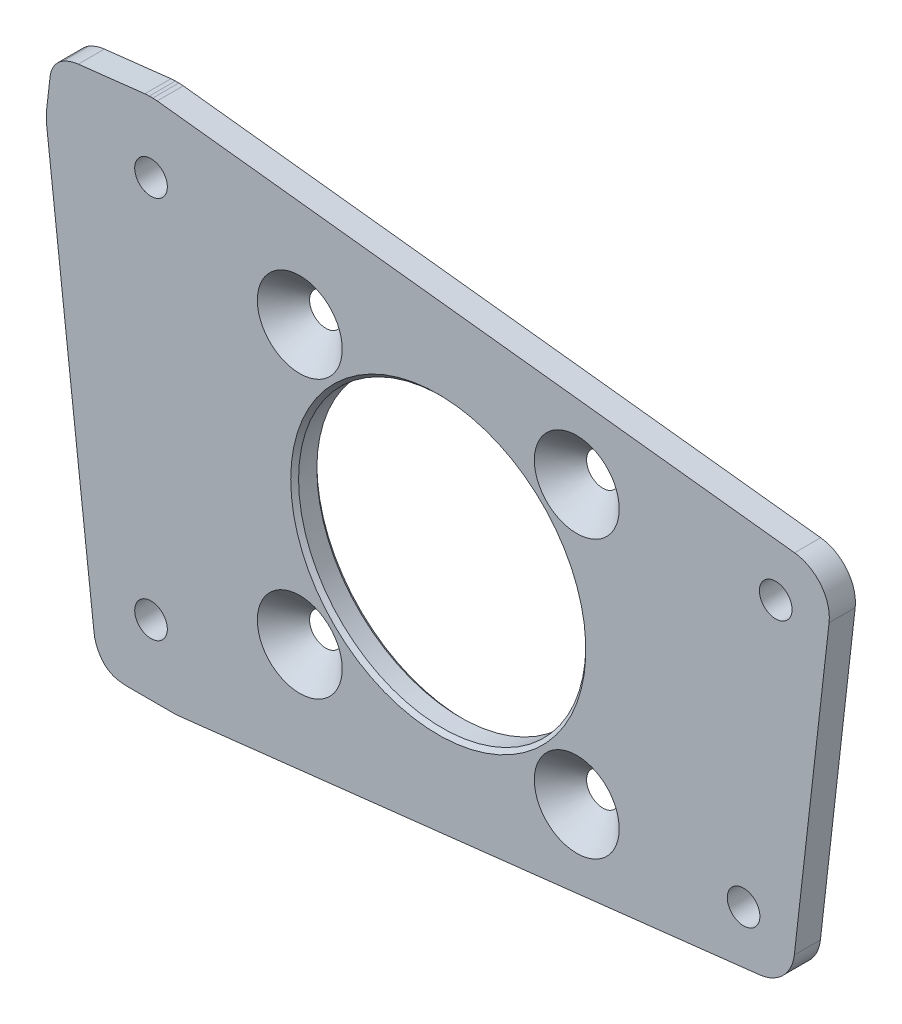
SolidWorks part; units mm, degrees
ref_plane "Płaszczyzna przednia" through (0, 0, 0) normal (0, 0, 1) x (1, 0, 0)
ref_plane "Płaszczyzna górna" through (0, 0, 0) normal (0, 1, 0) x (1, 0, 0)
ref_plane "Płaszczyzna prawa" through (0, 0, 0) normal (1, 0, 0) x (0, 0, -1)
sketch "Szkic1" plane through (0, 0, 0) normal (0, 0, 1) x (1, 0, 0)
  line L0 (0, 0) -> (-23.297, 23.297) construction
  line L1 (-27, -20) -> (27, -20)
  line L2 (-30, -17) -> (-30, 17)
  line L3 (-27, 20) -> (27, 20)
  line L4 (30, -17) -> (30, 17)
  line L5 (-30, -20) -> (30, 20) construction
  line L6 (-30, 20) -> (30, -20) construction
  line L7 (0, 0) -> (25.2349, 25.2349) construction
  arc A0 (27, 20) -> (30, 17) centre (27, 17) cw
  arc A1 (27, -20) -> (30, -17) centre (27, -17) ccw
  arc A2 (-27, -20) -> (-30, -17) centre (-27, -17) cw
  arc A3 (-30, 17) -> (-27, 20) centre (-27, 17) cw
  circle A4 centre (0, 0) radius 11
  circle A5 centre (-22, 14.6667) radius 1.25
  circle A8 centre (-10.6066, -10.6066) radius 1.25
  circle A9 centre (10.6066, -10.6066) radius 1.25
  circle A10 centre (10.6066, 10.6066) radius 1.25
  circle A11 centre (-10.6066, 10.6066) radius 1.25
  circle A12 centre (0, 0) radius 15 construction
  point P0 (0, 0)
  dimension "D3" = 3
  dimension "D4" = 30
  dimension "D6" = 2.5
  dimension "D7" = 2.5
  dimension "D8" = 2.5
  dimension "D9" = 2.5
  dimension "D10" = 22
  dimension "D11" = 2.5
  dimension "D1" = 60
  dimension "D2" = 40
  dimension "D5" = 45
  dimension "D12" = 8
extrude "Dodanie-wyciągnięcie1" add sketch "Szkic1" along normal blind 2
chamfer "Sfazowanie1" distance 0.3 angle 45 2 edges at (11, 0, 0) (11, 0, 2)
chamfer "Sfazowanie2" distance 2 angle 45 4 edges at (-9.3566, -10.6066, 2) (11.8566, -10.6066, 2) (11.8566, 10.6066, 2) (-9.3566, 10.6066, 2)
sketch "Szkic2" plane through (0, 0, 2) normal (0, 0, 1) x (1, 0, 0)
  line L9 (26.0813, 25.5127) -> (-27.5716, 19.3997)
  line L10 (-30.2127, 16.0794) -> (-26.3638, -17.7021)
  line L11 (-23.0435, -20.3432) -> (30.6094, -14.2302)
  line L12 (33.2505, -10.9099) -> (29.4016, 22.8716)
  arc A8 (29.4016, 22.8716) -> (26.0813, 25.5127) centre (26.4209, 22.532) ccw
  arc A9 (-27.5716, 19.3997) -> (-30.2127, 16.0794) centre (-27.232, 16.419) ccw
  arc A10 (-26.3638, -17.7021) -> (-23.0435, -20.3432) centre (-23.3831, -17.3625) ccw
  arc A11 (30.6094, -14.2302) -> (33.2505, -10.9099) centre (30.2698, -11.2495) ccw
sketch "Szkic3" plane through (0, 0, 0) normal (0, 0, 1) x (1, 0, 0)
  line L0 (-22, 14.6667) -> (-22, -14.6667) construction
  line L1 (25.8424, 10.5577) -> (-22, 14.6667) construction
  line L2 (-22, 14.6667) -> (23.383, -11.0277) construction
  line L3 (26, 16) -> (-22, 14.6667) construction
  line L4 (-22, 14.6667) -> (25.0697, 5.1682) construction
  line L5 (26, -5.725) -> (-22, 14.6667) construction
  line L6 (-22, 14.6667) -> (20.1826, -16) construction
  line L7 (-18.6794, -14.4781) -> (-22, 14.6667) construction
  line L8 (-22, 14.6667) -> (-25.3206, -14.4781) construction
  line L9 (-30, 17) -> (-30, -17) construction
  line L10 (-27, -20) -> (27, -20) construction
  line L11 (-27, -20) -> (27, -20) construction
  line L12 (30, -17) -> (30, 17) construction
  line L14 (27, 20) -> (-27, 20) construction
  line L15 (30, -17) -> (30, 17) construction
  circle A3 centre (-22, 14.6667) radius 29.3333 construction
  circle A4 centre (-22, 14.6667) radius 52.1519 construction
  arc A9 (-18.5379, -15.7201) -> (-18.8209, -13.2361) centre (-18.6794, -14.4781) ccw construction
  arc A10 (-25.4621, -15.7201) -> (-18.5379, -15.7201) centre (-22, 14.6667) ccw construction
  arc A11 (-25.1791, -13.2361) -> (-25.4621, -15.7201) centre (-25.3206, -14.4781) ccw construction
  arc A12 (-25.1791, -13.2361) -> (-18.8209, -13.2361) centre (-22, 14.6667) ccw construction
  circle A13 centre (-22, 14.6667) radius 48.0185 construction
  arc A18 (27.1505, -6.2137) -> (24.8495, -5.2362) centre (26, -5.725) ccw construction
  arc A19 (21.1937, -16.735) -> (27.1505, -6.2137) centre (-22, 14.6667) ccw construction
  arc A20 (19.1716, -15.265) -> (21.1937, -16.735) centre (20.1826, -16) ccw construction
  arc A21 (19.1716, -15.265) -> (24.8495, -5.2362) centre (-22, 14.6667) ccw construction
  circle A22 centre (-22, -14.6667) radius 1.25
  arc A27 (23.8444, 5.4154) -> (24.7505, 15.9653) centre (-22, 14.6667) ccw construction
  arc A28 (27.2495, 16.0347) -> (24.7505, 15.9653) centre (26, 16) ccw construction
  arc A29 (26.295, 4.9209) -> (27.2495, 16.0347) centre (-22, 14.6667) ccw construction
  arc A30 (23.8444, 5.4154) -> (26.295, 4.9209) centre (25.0697, 5.1682) ccw construction
  circle A31 centre (23.383, -11.0277) radius 1.25
  circle A32 centre (25.8424, 10.5577) radius 1.25
  dimension "D1" = 1.25
  dimension "D11" = 2.5
  dimension "D12" = 58.6667
  dimension "D13" = 104.3038
  dimension "D14" = 96.037
  dimension "D17" = 2.5
  dimension "D18" = 1.25
  dimension "D23" = 2.5
  dimension "D24" = 1.25
  dimension "D25" = 1.25
  dimension "D4" = 13
  dimension "D5" = 13
  dimension "D6" = 13
  dimension "D7" = 6.5
  dimension "D8" = 6.5
  dimension "D9" = 6.5
  dimension "D2" = 8
  dimension "D3" = 5.3333
  dimension "D10" = 13
  dimension "D15" = 4
  dimension "D16" = 4
  dimension "D19" = 13
  dimension "D20" = 13
  dimension "D21" = 4
  dimension "D22" = 4
extrude "Wytnij-wyciągnięcie1" cut sketch "Szkic3" along normal up to next
sketch "Szkic4" plane through (0, 0, 0) normal (0, 0, 1) x (1, 0, 0)
  line L4 (-30.8922, -19.2111) -> (22.7606, -25.3241)
  line L5 (-29.6844, 17.8906) -> (-33.5333, -15.8908)
  line L6 (27.2888, 14.4188) -> (-26.3641, 20.5317)
  line L7 (26.081, -22.683) -> (29.9299, 11.0984)
  arc A4 (-33.5333, -15.8908) -> (-30.8922, -19.2111) centre (-30.5526, -16.2304) ccw
  arc A5 (-26.3641, 20.5317) -> (-29.6844, 17.8906) centre (-26.7037, 17.551) ccw
  arc A6 (29.9299, 11.0984) -> (27.2888, 14.4188) centre (26.9492, 11.438) ccw
  arc A7 (22.7606, -25.3241) -> (26.081, -22.683) centre (23.1003, -22.3434) ccw
extrude "Wytnij-wyciągnięcie2" cut sketch "Szkic2" against normal through all flip side to cut
extrude "Wytnij-wyciągnięcie4" cut sketch "Szkic4" along normal through all flip side to cut
fillet "Zaokrąglenie2" radius 3 7 edges at (-20.0315, -20, 1) (-23.9685, -20, 1) (-21.6972, 20, 1) (-22.3028, 20, 1) (-30, 14.2124, 1) (-30, 15.1209, 1) (26.9972, -14.6418, 1)
fillet "Zaokrąglenie3" radius 2 2 edges at (-29.6268, 18.2259, 1) (-25.0131, -19.881, 1)
equation "\"D7@Szkic1\"=\"D6@Szkic1\""
equation "\"D8@Szkic1\"=\"D6@Szkic1\""
equation "\"D9@Szkic1\"=\"D6@Szkic1\""
equation "\"D7@Szkic3\"=\"D4@Szkic3\"/2"
equation "\"D8@Szkic3\"=\"D5@Szkic3\"/2"
equation "\"D9@Szkic3\"=\"D6@Szkic3\"/2"
equation "\"D25@Szkic3\"=\"D24@Szkic3\""
